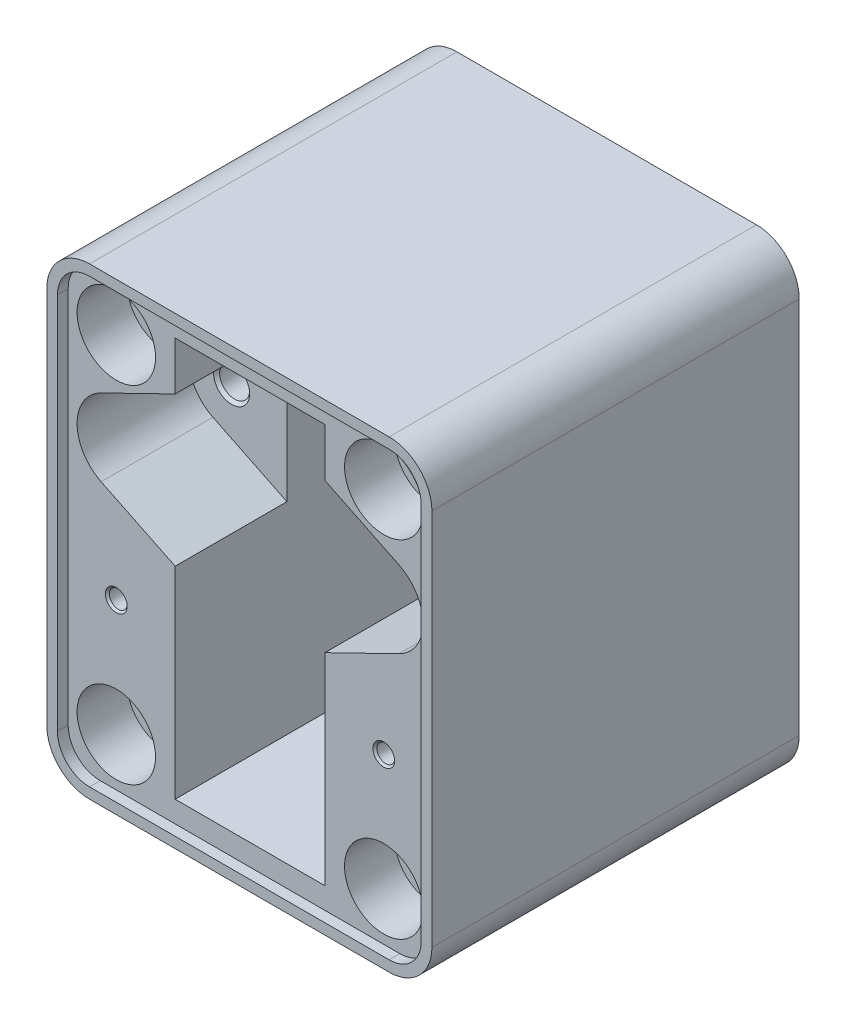
SolidWorks part; units mm, degrees
ref_plane "Front Plane" through (0, 0, 0) normal (0, 0, 1) x (1, 0, 0)
ref_plane "Top Plane" through (0, 0, 0) normal (0, 1, 0) x (1, 0, 0)
ref_plane "Right Plane" through (0, 0, 0) normal (1, 0, 0) x (0, 0, -1)
sketch "Sketch1" plane through (0, 0, 0) normal (0, 0, 1) x (1, 0, 0)
  line L1 (0, 0) -> (54, 0)
  line L2 (0, 0) -> (0, 65)
  line L3 (0, 65) -> (54, 65)
  line L4 (54, 0) -> (54, 65)
  dimension "D1" = 65
  dimension "D2" = 54
extrude "Boss-Extrude1" add sketch "Sketch1" along normal blind 50
sketch "Sketch2" plane through (0, 0, 50) normal (0, 0, 1) x (1, 0, 0)
  line L1 (16.5, 53.25) -> (37.5, 53.25)
  line L2 (16.5, 53.25) -> (16.5, 11.75)
  line L3 (16.5, 11.75) -> (37.5, 11.75)
  line L4 (37.5, 53.25) -> (37.5, 11.75)
  line L6 (0, 65) -> (0, 0) construction
  line L7 (54, 65) -> (0, 65) construction
  dimension "D1" = 41.5
  dimension "D2" = 21
  dimension "D3" = 16.5
  dimension "D4" = 11.75
extrude "Cut-Extrude1" cut sketch "Sketch2" against normal through all contours L2 L3 L4 L1
fillet "Fillet1" radius 6 4 edges at (0, 65, 25) (0, 0, 25) (54, 65, 25) (54, 0, 25)
sketch "Sketch3" plane through (0, 0, 50) normal (0, 0, 1) x (1, 0, 0)
  line L0 (16.5, 53.25) -> (37.5, 53.25) construction
  line L1 (16.5, 60.5) -> (37.5, 60.5)
  line L2 (16.5, 60.5) -> (16.5, 4.5)
  line L3 (16.5, 4.5) -> (37.5, 4.5)
  line L4 (37.5, 60.5) -> (37.5, 4.5)
  line L5 (16.5, 11.75) -> (37.5, 11.75) construction
  line L6 (37.5, 53.25) -> (37.5, 11.75) construction
  line L7 (16.5, 53.25) -> (16.5, 11.75) construction
  dimension "D1" = 7.25
  dimension "D2" = 7.25
extrude "Cut-Extrude2" cut sketch "Sketch3" against normal blind 42 contours L2 L3 L4 L1
sketch "Sketch4" plane through (0, 0, 50) normal (0, 0, 1) x (1, 0, 0)
  line L0 (16.5, 53.25) -> (37.5, 53.25) construction
  line L1 (27, 43.25) -> (27, 20.577) construction
  line L2 (8.75, 43.25) -> (45.25, 43.25) construction
  line L3 (32.9178, 55.3838) -> (47.661, 48.1934)
  line L4 (47.661, 38.3066) -> (32.9178, 31.1162)
  line L5 (21.0822, 31.1162) -> (6.339, 38.3066)
  line L6 (6.339, 48.1934) -> (21.0822, 55.3838)
  arc A0 (21.0822, 31.1162) -> (32.9178, 31.1162) centre (27, 43.25) ccw
  arc A1 (47.661, 38.3066) -> (47.661, 48.1934) centre (45.25, 43.25) ccw
  arc A2 (13.7106, 40.8747) -> (14.25, 43.25) centre (8.75, 43.25) ccw construction
  arc A3 (32.9178, 55.3838) -> (21.0822, 55.3838) centre (27, 43.25) ccw
  arc A4 (13.7106, 45.6253) -> (13.7106, 40.8747) centre (27, 43.25) ccw construction
  arc A5 (6.339, 48.1934) -> (6.339, 38.3066) centre (8.75, 43.25) ccw
  point P6 (-9.7018, 40.174)
  dimension "D4" = 27
  dimension "D5" = 11
  dimension "D6" = 5.5
  dimension "D1" = 10
  dimension "D2" = 36.5
  dimension "D3" = 27
extrude "Cut-Extrude-Thin3" cut sketch "Sketch4" against normal blind 15.67 thin thin type one direction wall 0.5
extrude "Cut-Extrude3" cut sketch "Sketch4<3>" against normal blind 15.67
sketch "Sketch4<3>" plane through (0, 0, 50) normal (0, 0, 1) x (1, 0, 0) same geometry as "Sketch4"
hole_wizard "M5 Tapped Hole1" positions "3DSketch1" profile "Sketch6" tap size "M5" standard "ISO"
sketch3d "3DSketch1"
  arc A2 (6.1199, 48.6428, 34.33) -> (6.1199, 37.8572, 34.33) centre (8.75, 43.25, 34.33) ccw construction
  point P0 (8.75, 43.25, 34.33)
  point P2 (45.25, 43.25, 34.33)
  point P18 (8.75, 43.25, 40.33)
  dimension "D1" = 36.5
  dimension "D2" = 0
sketch "Sketch6" plane through (8.75, 43.25, 34.33) normal (1, 0, 0) x (0, -1, 0)
  line L0 (0, 0) -> (0, 16.2618)
  line L1 (0, 16.2618) -> (2.1, 15)
  line L2 (2.1, 15) -> (2.1, 0.425)
  line L3 (2.1, 0.425) -> (2.525, 0)
  line L5 (2.525, 0) -> (0, 0)
  line L6 (-2.1, 0.425) -> (-2.525, 0) construction
  line L10 (0, 16.2618) -> (-2.1, 15) construction
  line L11 (0, -6.35) -> (0, 107.95) construction
  dimension "Tap Drill Dia." = 4.2
  dimension "Tap Drill Depth" = 15
  dimension "Near C'Sink Dia." = 5.05
  dimension "Near C'Sink Angle" = 90
  dimension "Drill Angle" = 118
cosmetic thread "Hole Thread1" parameters "D1"=15, "D2"=5
cosmetic thread "Hole Thread2" parameters "D1"=15, "D2"=5
hole_wizard "M3 Tapped Hole1" positions "3DSketch2" profile "Sketch7" tap size "M3" standard "ISO" end condition through all
sketch3d "3DSketch2"
  line L1 (16.5, 60.5, 8) -> (16.5, 53.25, 8) construction
  line L6 (16.5, 53.25, 8) -> (37.5, 53.25, 8) construction
  point P0 (22, 56.85, 8)
  point P2 (32, 56.85, 8)
  point P4 (32, 8.15, 8)
  point P6 (22, 8.15, 8)
  dimension "D1" = 10
  dimension "D2" = 5.5
  dimension "D3" = 48.7
  dimension "D4" = 3.6
cosmetic thread "Hole Thread3" parameters "D2"=3
cosmetic thread "Hole Thread4" parameters "D2"=3
cosmetic thread "Hole Thread5" parameters "D2"=3
cosmetic thread "Hole Thread6" parameters "D2"=3
sketch "Sketch7" plane through (22, 56.85, 8) normal (1, 0, 0) x (0, -1, 0)
  line L0 (0, 0) -> (0, 8)
  line L1 (0, 8) -> (1.25, 8)
  line L2 (1.25, 8) -> (1.25, 0.275)
  line L3 (1.25, 0.275) -> (1.525, 0)
  line L5 (1.525, 0) -> (0, 0)
  line L6 (-1.25, 0.275) -> (-1.525, 0) construction
  line L11 (0, -6.35) -> (0, 107.95) construction
  dimension "Thru Tap Drill Dia." = 2.5
  dimension "Thru Tap Drill Depth" = 8
  dimension "Near C'Sink Dia." = 3.05
  dimension "Near C'Sink Angle" = 90
hole_wizard "Hole1" positions "3DSketch3" profile "Sketch9" legacy end condition through all
sketch3d "3DSketch3"
  line L1 (0, 59, 50) -> (0, 6, 50) construction
  line L3 (48, 65, 50) -> (6, 65, 50) construction
  line L5 (37.5, 60.5, 50) -> (37.5, 53.7053, 50) construction
  line L6 (37.5, 32.7947, 50) -> (37.5, 4.5, 50) construction
  line L7 (6, 0, 50) -> (48, 0, 50) construction
  point P0 (8.25, 56.75, 50)
  point P2 (45.75, 56.75, 50)
  point P4 (45.75, 8.25, 50)
  point P6 (8.25, 8.25, 50)
  point P32 (0, 0, 0)
  dimension "D1" = 8.25
  dimension "D2" = 8.25
  dimension "D3" = 8.25
  dimension "D4" = 8.25
  dimension "D5" = 8.25
  dimension "D6" = 8.25
sketch "Sketch9" plane through (8.25, 56.75, 50) normal (1, 0, 0) x (0, -1, 0)
  line L0 (0, 0) -> (0, 50)
  line L1 (0, 50) -> (3.25, 50)
  line L2 (3.25, 50) -> (3.25, 7)
  line L3 (3.25, 7) -> (5.5, 7)
  line L4 (5.5, 7) -> (5.5, 0)
  line L5 (5.5, 0) -> (0, 0)
  line L6 (0, 110) -> (0, -10) construction
  dimension "Diameter" = 6.5
  dimension "Depth" = 50
  dimension "C-Bore Diameter" = 11
  dimension "C-Bore Depth" = 7
sketch "Sketch10" plane through (0, 0, 50) normal (0, 0, 1) x (1, 0, 0)
  line L4 (48, 65) -> (6, 65)
  line L5 (0, 59) -> (0, 6)
  line L6 (6, 0) -> (48, 0)
  line L7 (54, 6) -> (54, 59)
  line L8 (48, 65) -> (6, 65)
  line L9 (0, 59) -> (0, 6)
  line L10 (6, 0) -> (48, 0)
  line L11 (54, 6) -> (54, 59)
  arc A4 (6, 65) -> (0, 59) centre (6, 59) ccw
  arc A5 (0, 6) -> (6, 0) centre (6, 6) ccw
  arc A6 (48, 0) -> (54, 6) centre (48, 6) ccw
  arc A7 (54, 59) -> (48, 65) centre (48, 59) ccw
  arc A8 (6, 65) -> (0, 59) centre (6, 59) ccw
  arc A9 (0, 6) -> (6, 0) centre (6, 6) ccw
  arc A10 (48, 0) -> (54, 6) centre (48, 6) ccw
  arc A11 (54, 59) -> (48, 65) centre (48, 59) ccw
  dimension "D1" = 0
extrude "Extrude-Thin1" add sketch "Sketch10" along normal blind 1.5 thin thin type one direction reverse wall 1.5
hole_wizard "M3 Tapped Hole2" positions "3DSketch4" profile "Sketch11" tap size "M3" standard "ISO" end condition through all
sketch3d "3DSketch4"
  line L0 (16.5, 32.7947, 50) -> (16.5, 4.5, 50) construction
  line L1 (37.5, 32.7947, 50) -> (37.5, 4.5, 50) construction
  point P0 (8.25, 24.5509, 50)
  point P2 (45.75, 24.5509, 50)
  point P5 (0, 0, 0)
  dimension "D1" = 8.25
  dimension "D2" = 8.25
sketch "Sketch11" plane through (8.25, 24.5509, 50) normal (1, 0, 0) x (0, -1, 0)
  line L0 (0, 0) -> (0, 50)
  line L1 (0, 50) -> (1.25, 50)
  line L2 (1.25, 50) -> (1.25, 0.275)
  line L3 (1.25, 0.275) -> (1.525, 0)
  line L5 (1.525, 0) -> (0, 0)
  line L6 (-1.25, 0.275) -> (-1.525, 0) construction
  line L11 (0, -6.35) -> (0, 107.95) construction
  dimension "Thru Tap Drill Dia." = 2.5
  dimension "Thru Tap Drill Depth" = 50
  dimension "Near C'Sink Dia." = 3.05
  dimension "Near C'Sink Angle" = 90
cosmetic thread "Hole Thread7" parameters "D2"=3
cosmetic thread "Hole Thread8" parameters "D2"=3
